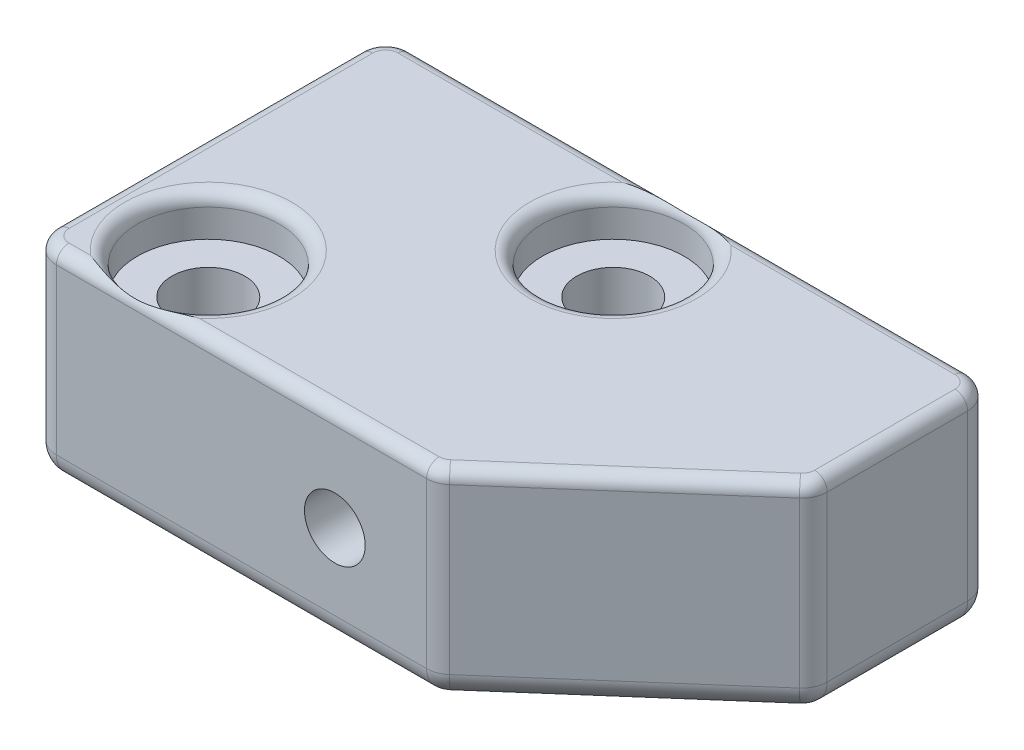
SolidWorks part; units mm, degrees
ref_plane "Front Plane" through (0, 0, 0) normal (0, 0, 1) x (1, 0, 0)
ref_plane "Top Plane" through (0, 0, 0) normal (0, 1, 0) x (1, 0, 0)
ref_plane "Right Plane" through (0, 0, 0) normal (1, 0, 0) x (0, 0, -1)
sketch "Sketch1" plane through (0, 0, 0) normal (0, 1, 0) x (1, 0, 0)
  line L0 (-19.05, 0) -> (19.05, 0)
  line L1 (-19.05, 0) -> (-19.05, -22.225)
  line L2 (-19.05, -22.225) -> (6.35, -22.225)
  line L3 (6.35, -22.225) -> (19.05, -11.1125)
  line L4 (19.05, -11.1125) -> (19.05, 0)
  point P4 (0, 0)
  dimension "D1" = 38.1
  dimension "D2" = 11.1125
  dimension "D3" = 22.225
  dimension "D4" = 25.4
extrude "Boss-Extrude1" add sketch "Sketch1" along normal blind 12.7
sketch "Sketch2" plane through (0, 12.7, 0) normal (0, 1, 0) x (1, 0, 0)
  line L0 (-19.05, -11.1125) -> (19.05, -11.1125) construction
  line L1 (-19.05, 0) -> (-19.05, -22.225) construction
  circle A0 centre (0, -4.7625) radius 2.286
  circle A1 centre (-12.7, -17.4625) radius 2.286
  point P9 (0, 0)
  dimension "D4" = 4.572
  dimension "D5" = 4.572
  dimension "D1" = 6.35
  dimension "D2" = 6.35
  dimension "D3" = 6.35
extrude "Cut-Extrude1" cut sketch "Sketch2" against normal through all
sketch "Sketch3" plane through (0, 12.7, 0) normal (0, 1, 0) x (1, 0, 0)
  circle A0 centre (0, -4.7625) radius 4.445
  circle A1 centre (-12.7, -17.4625) radius 4.445
  dimension "D1" = 8.89
extrude "Cut-Extrude2" cut sketch "Sketch3" against normal blind 2.54
sketch "Sketch4" plane through (0, 0, 0) normal (0, 0, -1) x (-1, 0, 0)
  line L0 (-12.7, 6.35) -> (12.7, 6.35) construction
  circle A0 centre (-12.7, 6.35) radius 1.905
  circle A1 centre (12.7, 6.35) radius 1.905
  point P4 (0, 6.35)
  dimension "D3" = 3.81
  dimension "D1" = 6.35
  dimension "D2" = 25.4
extrude "Cut-Extrude3" cut sketch "Sketch4" against normal blind 12.7
sketch "Sketch5" plane through (0, 0, 22.225) normal (0, 0, 1) x (1, 0, 0)
  circle A0 centre (0, 6.35) radius 1.905
  point P2 (0, 0)
  dimension "D2" = 3.81
  dimension "D1" = 6.35
extrude "Cut-Extrude4" cut sketch "Sketch5" against normal blind 12.7
fillet "Fillet1" radius 1.5875 10 edges at (0, 0, 0) (-6.35, 0, 22.225) (19.05, 6.35, 0) (19.05, 0, 5.5562) (19.05, 6.35, 11.1125) (12.7, 0, 16.6687) (6.35, 6.35, 22.225) (-19.05, 6.35, 0) (-19.05, 6.35, 22.225) (-19.05, 0, 11.1125)
fillet "Fillet2" radius 0.7937 12 edges at (18.585, 12.7, 0.465) (19.05, 12.7, 5.9898) (18.9081, 12.7, 11.0481) (12.6534, 12.7, 16.7095) (6.3119, 12.7, 22.1236) (-5.8545, 12.7, 22.225) (-18.585, 12.7, 21.76) (-19.05, 12.7, 11.1125) (-18.585, 12.7, 0.465) (0, 12.7, 0) (0, 12.7, 9.2075) (-12.7, 12.7, 21.9075)
